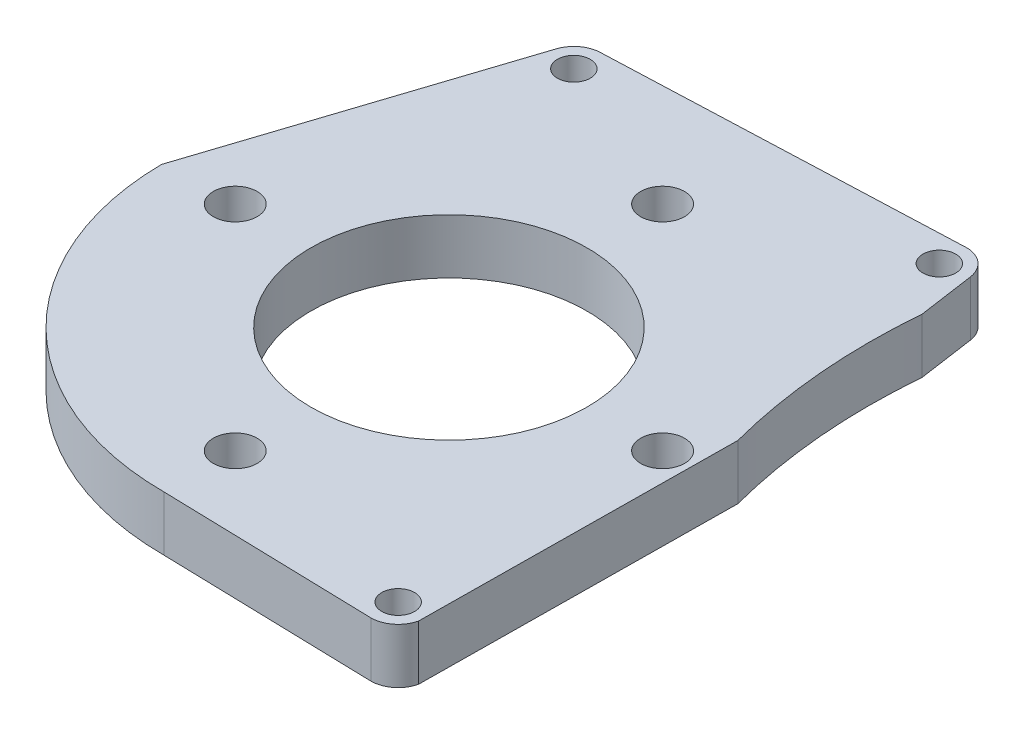
SolidWorks part; units mm, degrees
ref_plane "前视基准面" through (0, 0, 0) normal (0, 0, 1) x (1, 0, 0)
ref_plane "上视基准面" through (0, 0, 0) normal (0, 1, 0) x (1, 0, 0)
ref_plane "右视基准面" through (0, 0, 0) normal (1, 0, 0) x (0, 0, -1)
sketch "Sketch1" plane through (0, 0, 0) normal (0, 1, 0) x (1, 0, 0)
  line L0 (22.0503, 22.6744) -> (21.2853, 27.9947)
  line L1 (17.326, 31.4254) -> (-14.9041, 30.1394)
  line L2 (-27.5, 0) -> (-18.5466, 27.3856)
  line L3 (23.6168, 4.445) -> (23.3142, -24.7546)
  line L4 (0, -27.5) -> (19.3835, -28.0131)
  line L5 (22.1148, 4.2573) -> (21.8158, -24.591)
  line L6 (20.5409, 22.6328) -> (19.8006, 27.7812)
  line L7 (17.3524, 29.9253) -> (-14.8443, 28.6406)
  line L8 (-25.9989, -0.2357) -> (-17.1209, 26.9195)
  line L9 (0.0196, -26) -> (19.4011, -26.513)
  arc A0 (-27.5, 0) -> (0, -27.5) centre (0, 0) ccw
  circle A1 centre (0, 0) radius 19.5 construction
  circle A2 centre (0, 19.5) radius 2
  circle A3 centre (19.5, 0) radius 2
  circle A4 centre (0, -19.5) radius 2
  circle A5 centre (-19.5, 0) radius 2
  circle A6 centre (0, 0) radius 12.6
  circle A7 centre (-14.7447, 26.1426) radius 1.5
  circle A8 centre (17.326, 27.4254) radius 1.5
  circle A9 centre (19.3835, -24.0131) radius 1.5
  arc A10 (22.0503, 22.6744) -> (23.6168, 4.445) centre (74.3406, 17.9856) ccw
  arc A11 (21.2853, 27.9947) -> (17.326, 31.4254) centre (17.326, 27.4254) ccw
  arc A12 (-14.9041, 30.1394) -> (-18.5466, 27.3856) centre (-14.7447, 26.1426) ccw
  arc A14 (19.3835, -28.0131) -> (23.3142, -24.7546) centre (19.3835, -24.0131) ccw
  arc A15 (19.4011, -26.513) -> (21.8158, -24.591) centre (19.3835, -24.0131) ccw
  arc A16 (20.5409, 22.6328) -> (22.1148, 4.2573) centre (74.3406, 17.9856) ccw
  arc A17 (19.8006, 27.7812) -> (17.3524, 29.9253) centre (17.326, 27.4254) ccw
  arc A18 (-14.8443, 28.6406) -> (-17.1209, 26.9195) centre (-14.7447, 26.1426) ccw
  arc A19 (-25.9989, -0.2357) -> (0.0196, -26) centre (0, 0) ccw
  point P14 (0, 0)
  dimension "D1" = 55
  dimension "D2" = 39
  dimension "D3" = 4
  dimension "D5" = 25.2
  dimension "D6" = 3
  dimension "D7" = 3
  dimension "D8" = 3
  dimension "D9" = 105
  dimension "D10" = 8
  dimension "D11" = 8
  dimension "D12" = 1.5
  dimension "D4" = 4
extrude "Boss-Extrude1" add sketch "Sketch1" along normal blind 5 contours L8 A19 L9 A15 L5 A16 L6 A17 L7 A18 A9 A8 A7 A6 A5 A4 A3 A2 region at (21.2237, 0, 10.1592)
